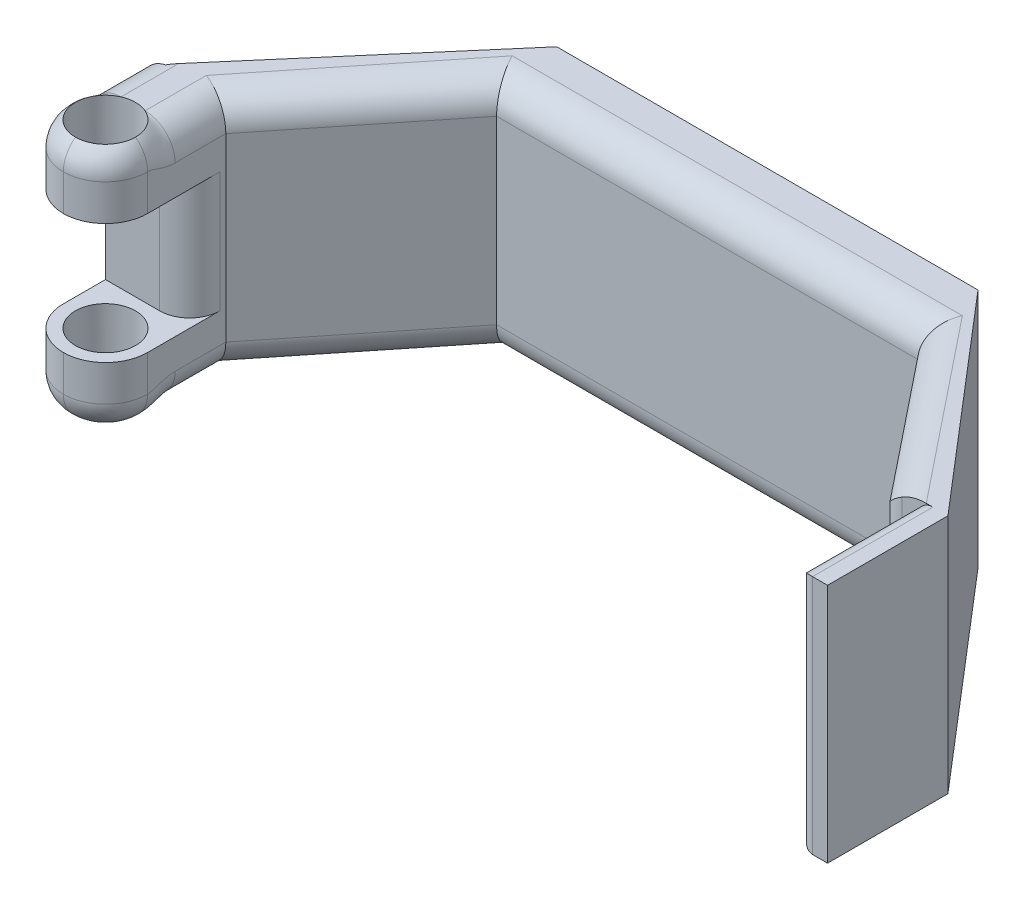
SolidWorks part; units mm, degrees
ref_plane "Front Plane" through (0, 0, 0) normal (0, 0, 1) x (1, 0, 0)
ref_plane "Top Plane" through (0, 0, 0) normal (0, 1, 0) x (1, 0, 0)
ref_plane "Right Plane" through (0, 0, 0) normal (1, 0, 0) x (0, 0, -1)
sketch "Sketch1" plane through (0, 0, 0) normal (0, 1, 0) x (1, 0, 0)
  line L0 (0, 0) -> (20, 25)
  line L1 (20, 25) -> (90, 25)
  line L2 (90, 25) -> (110, 0)
  line L3 (0, 0) -> (-10, 0)
  line L4 (-10, 0) -> (20, 35)
  line L5 (20, 35) -> (90, 35)
  line L6 (110, 0) -> (120, 0)
  line L7 (120, 0) -> (90, 35)
  dimension "D1" = 20
  dimension "D2" = 25
  dimension "D3" = 70
  dimension "D4" = 20
  dimension "D5" = 25
  dimension "D6" = 10
  dimension "D7" = 10
  dimension "D8" = 10
extrude "Boss-Extrude1" add sketch "Sketch1" along normal blind 40
sketch "Sketch2" plane through (0, 0, 0) normal (0, 0, 1) x (1, 0, 0)
  line L1 (0, 40) -> (-14, 40)
  line L2 (0, 40) -> (0, 0)
  line L3 (0, 0) -> (-14, 0)
  line L4 (-14, 40) -> (-14, 0)
  dimension "D1" = 14
extrude "Boss-Extrude2" add sketch "Sketch2" along normal blind 20
sketch "Sketch3" plane through (0, 0, 0) normal (1, 0, 0) x (0, 0, -1)
  line L0 (-20, 0) -> (-20, 40) construction
  line L1 (-20, 30) -> (-6, 30)
  line L2 (-20, 30) -> (-20, 10)
  line L3 (-20, 10) -> (-6, 10)
  line L4 (-6, 30) -> (-6, 10)
  line L5 (-20, 0) -> (0, 0) construction
  dimension "D1" = 14
  dimension "D2" = 20
  dimension "D3" = 10
extrude "Cut-Extrude2" cut sketch "Sketch3" against normal up to next
sketch "Sketch5" plane through (0, 10, 0) normal (0, 1, 0) x (1, 0, 0)
  circle A0 centre (-7, -13) radius 5
  dimension "D1" = 10
extrude "Cut-Extrude3" cut sketch "Sketch5" against normal through all and the other way through all
fillet "Fillet1" radius 7 4 edges at (-14, 5, 20) (0, 5, 20) (0, 35, 20) (-14, 35, 20)
sketch "Sketch7" plane through (0, 0, 0) normal (0, 0, 1) x (1, 0, 0)
  line L0 (110, 0) -> (120, 0) construction
  line L1 (120, 40) -> (115, 40)
  line L2 (120, 40) -> (120, 0)
  line L3 (120, 0) -> (115, 0)
  line L4 (115, 40) -> (115, 0)
extrude "Boss-Extrude3" add sketch "Sketch7" along normal blind 20
fillet "Fillet2" radius 5 12 edges at (0, 0, 6.5) (-14, 0, 6.5) (-14, 40, 6.5) (0, 40, 6.5) (0, 20, 6) (110, 20, 0) (100, 40, -12.5) (100, 0, -12.5) (55, 0, -25) (10, 0, -12.5) (55, 40, -25) (10, 40, -12.5)
fillet "Fillet3" radius 2.5 3 edges at (115, 20, 20) (115, 0, 9.123) (115, 40, 9.123)
